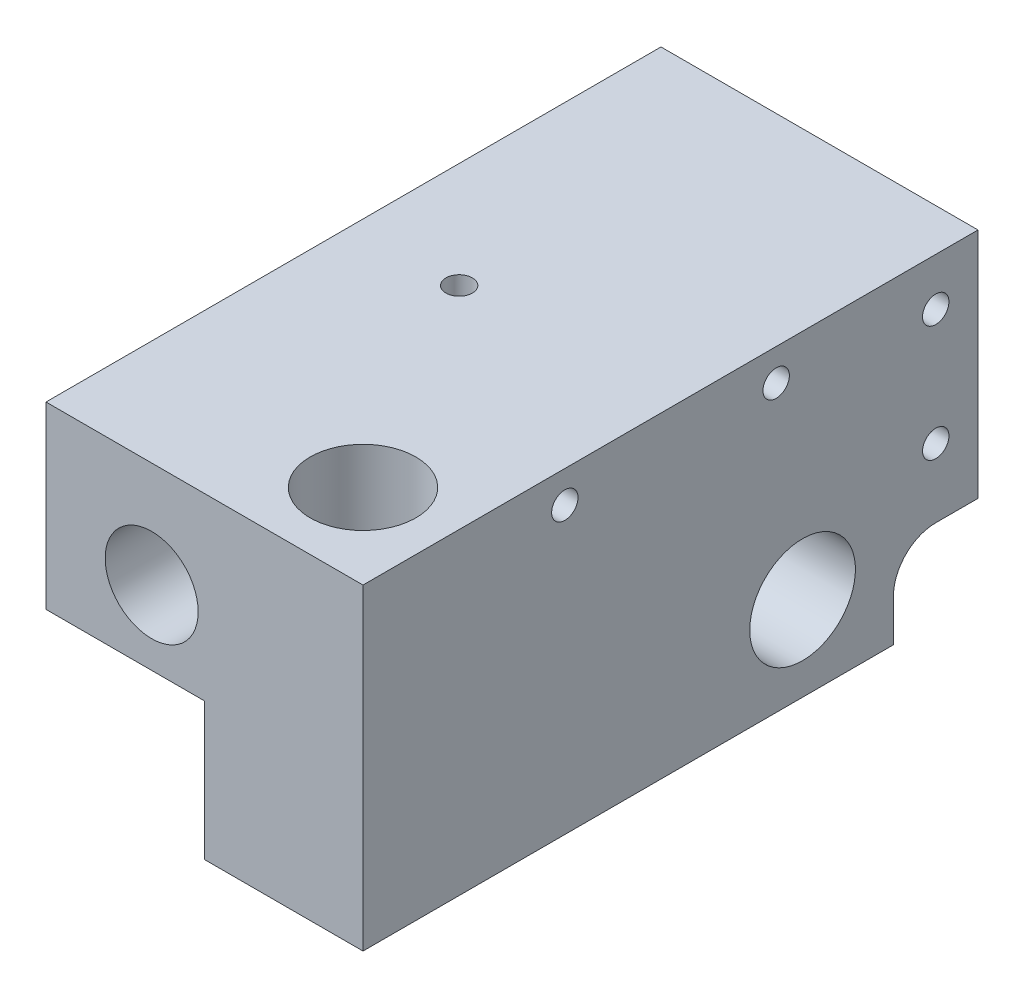
SolidWorks part; units mm, degrees
material "6061-T4 (SS)"
ref_plane "Piano frontale" through (0, 0, 0) normal (0, 0, 1) x (1, 0, 0)
ref_plane "Piano superiore" through (0, 0, 0) normal (0, 1, 0) x (1, 0, 0)
ref_plane "Piano destro" through (0, 0, 0) normal (1, 0, 0) x (0, 0, -1)
sketch "Schizzo1" plane through (0, 0, 0) normal (0, 0, 1) x (1, 0, 0)
  line L1 (0, 0) -> (30, 0)
  line L2 (0, 0) -> (0, 30)
  line L3 (0, 30) -> (30, 30)
  line L4 (30, 0) -> (30, 30)
  dimension "D1" = 30
extrude "Estrusione-Estrusione1" add sketch "Schizzo1" along normal blind 58.2
sketch "Schizzo2" plane through (0, 0, 0) normal (0, -1, 0) x (1, 0, 0)
  line L1 (0, 58.2) -> (30, 58.2) construction
  line L3 (30, 58.2) -> (30, 0) construction
  circle A0 centre (22, 50.2) radius 5
  dimension "D1" = 10
  dimension "D3" = 3
  dimension "D2" = 3
extrude "Taglio-Estrusione1" cut sketch "Schizzo2" against normal up to next
ref_point "Punto1"
sketch "Schizzo3" plane through (0, 0, 0) normal (-1, 0, 0) x (0, 0, 1)
  line L0 (50.2, 0) -> (50.2, 8) construction
  line L1 (50.2, 8) -> (16.6, 8) construction
  line L2 (58.2, 30) -> (58.2, 0) construction
  line L3 (58.2, 0) -> (0, 0) construction
  circle A0 centre (16.6, 8) radius 5
  dimension "D1" = 10
  dimension "D3" = 3
  dimension "D2" = 33.6
  dimension "D4" = 41.6
extrude "Taglio-Estrusione2" cut sketch "Schizzo3" against normal up to next
sketch "Schizzo5" plane through (0, 0, 0) normal (0, 0, -1) x (-1, 0, 0)
  line L0 (0, 30) -> (-30, 0) construction
  line L3 (0, 30) -> (-30, 30) construction
  line L5 (0, 30) -> (0, 0) construction
  circle A1 centre (-10, 20) radius 3
  dimension "D1" = 10
  dimension "D2" = 10
  dimension "D4" = 6
hole_wizard "Foro filettato G1/8-1" positions "Schizzo3D1" profile "Schizzo8" tap size "G1/8" standard "BSI"
sketch3d "Schizzo3D1"
  line L1 (30, 30, 58.2) -> (0, 30, 58.2) construction
  line L2 (0, 30, 58.2) -> (0, 0, 58.2) construction
  point P0 (10, 20, 58.2)
  dimension "D1" = 10
  dimension "D2" = 10
sketch "Schizzo8" plane through (10, 20, 58.2) normal (1, 0, 0) x (0, -1, 0)
  line L0 (0, 0) -> (0, 12.6438)
  line L1 (0, 12.6438) -> (4.4, 10)
  line L2 (4.4, 10) -> (4.4, 0)
  line L5 (4.4, 0) -> (0, 0)
  line L10 (0, 12.6438) -> (-4.4, 10) construction
  line L11 (0, -6.35) -> (0, 107.95) construction
  dimension "Tap Drill Dia." = 8.8
  dimension "Tap Drill Depth" = 10
  dimension "Drill Angle" = 118
sketch "Schizzo20" plane through (0, 0, 0) normal (-1, 0, 0) x (0, 0, 1)
  line L0 (4, 8) -> (0, 8)
  line L1 (0, 0) -> (8, 0) construction
  line L2 (0, 0) -> (0, 8) construction
  line L3 (0, 8) -> (8, 8) construction
  line L4 (8, 0) -> (8, 8) construction
  line L5 (0, 8) -> (0, 0)
  line L6 (0, 0) -> (8, 0)
  line L7 (8, 0) -> (8, 4)
  arc A1 (8, 4) -> (4, 8) centre (4, 4) ccw
  dimension "D1" = 8
  dimension "D2" = 8
  dimension "D3" = 8
extrude "Taglio-Estrusione5" cut sketch "Schizzo20" against normal blind 10
sketch "Schizzo21" plane through (30, 0, 0) normal (1, 0, 0) x (0, 0, -1)
  line L0 (-8, 0) -> (-8, 4) construction
  line L2 (-4, 8) -> (0, 8) construction
  line L3 (0, 8) -> (0, 0) construction
  line L4 (-8, 0) -> (-8, 4)
  line L5 (0, 0) -> (-8, 0)
  line L6 (-4, 8) -> (0, 8)
  line L7 (0, 8) -> (0, 0)
  arc A0 (-4, 8) -> (-8, 4) centre (-4, 4) ccw construction
  arc A1 (-4, 8) -> (-8, 4) centre (-4, 4) ccw
extrude "Taglio-Estrusione6" cut sketch "Schizzo21" against normal blind 10
sketch "Schizzo23" plane through (10, 0, 0) normal (-1, 0, 0) x (0, 0, 1)
  line L0 (0, 0) -> (8, 0) construction
  line L1 (0, 8) -> (0, 0) construction
  circle A0 centre (3, 3) radius 1.5
  point P2 (4, 0)
  dimension "D3" = 3
  dimension "D1" = 3
  dimension "D2" = 3
extrude "Taglio-Estrusione7" cut sketch "Schizzo23" against normal up to surface (10 mm away) up to face at (20, 4.1657, 4.1657)
sketch "Schizzo25" plane through (30, 0, 0) normal (1, 0, 0) x (0, 0, -1)
  line L0 (-58.2, 30) -> (0, 30) construction
  line L2 (-58.2, 0) -> (-58.2, 30) construction
  point P0 (-39.1, 27)
  point P1 (-19.1, 27)
  point P8 (-58.2, 28.5095)
  dimension "D1" = 3
  dimension "D2" = 19.1
  dimension "D3" = 39.1
hole_wizard "Foro filettato M3-2" positions "Schizzo3D2" profile "Schizzo27" tap size "M3" standard "ISO"
sketch3d "Schizzo3D2"
  point P0 (30, 27, 39.1)
  point P3 (30, 27, 19.1)
sketch "Schizzo27" plane through (30, 27, 39.1) normal (0, 1, 0) x (0, 0, -1)
  line L0 (0, 0) -> (0, 12.2511)
  line L1 (0, 12.2511) -> (1.25, 11.5)
  line L2 (1.25, 11.5) -> (1.25, 0)
  line L5 (1.25, 0) -> (0, 0)
  line L10 (0, 12.2511) -> (-1.25, 11.5) construction
  line L11 (0, -6.35) -> (0, 107.95) construction
  dimension "Tap Drill Dia." = 2.5
  dimension "Tap Drill Depth" = 11.5
  dimension "Drill Angle" = 118
cosmetic thread "Filettatura del foro2" parameters "D1"=10, "D2"=3
cosmetic thread "Filettatura del foro3" parameters "D1"=10, "D2"=3
sketch "Schizzo29" plane through (0, 0, 0) normal (-1, 0, 0) x (0, 0, 1)
  line L0 (20.2683, 0) -> (58.2, 0)
  line L1 (58.2, 0) -> (58.2, 13)
  line L2 (58.2, 13) -> (58.2, 0)
  line L5 (58.2, 0) -> (58.2, 30) construction
  line L7 (58.2, 0) -> (8, 0) construction
  line L8 (42.2, 13) -> (58.2, 13)
  arc A1 (42.2, 13) -> (20.2683, 0) centre (42.2, -12) ccw
  line M6 (8, 0) -> (58.2, 0)
  line M7 (58.2, 0) -> (58.2, 30)
  dimension "D3" = 25
  dimension "D1" = 16
  dimension "D2" = 12
extrude "Taglio-Estrusione11" cut sketch "Schizzo29" against normal blind 15 contours L8 A1 M6 M7 region at (0, 5.9257, 41.9996)
sketch "Schizzo30" plane through (0, 30, 0) normal (0, 1, 0) x (1, 0, 0)
  line L0 (10, 0) -> (10, -58.2) construction
  line L1 (30, 0) -> (0, 0) construction
  line L2 (30, -58.2) -> (30, 0) construction
  line L3 (0, -29.1) -> (30, -29.1) construction
  line L4 (0, -58.2) -> (0, 0) construction
  line L5 (30, -58.2) -> (0, -58.2) construction
  point P4 (10, -29.1)
  dimension "D1" = 20
  dimension "D2" = 29.1
hole_wizard "Foro filettato M3-3" positions "Schizzo3D4" profile "Schizzo31" tap size "M3" standard "DIN"
sketch3d "Schizzo3D4"
  point P0 (10, 30, 29.1)
  point P2 (10, 30, 29.1)
  point P4 (10, 30, 29.1)
  point P7 (10, 30, 29.1)
  point P9 (10, 30, 29.1)
sketch "Schizzo31" plane through (10, 30, 29.1) normal (1, 0, 0) x (0, 0, 1)
  line L0 (0, 0) -> (0, 5.7511)
  line L1 (0, 5.7511) -> (1.25, 5)
  line L2 (1.25, 5) -> (1.25, 0)
  line L5 (1.25, 0) -> (0, 0)
  line L10 (0, 5.7511) -> (-1.25, 5) construction
  line L11 (0, -6.35) -> (0, 107.95) construction
  dimension "Tap Drill Dia." = 2.5
  dimension "Tap Drill Depth" = 5
  dimension "Drill Angle" = 118
hole_wizard "Foro Ø16.0 (16)-1" positions "Schizzo3D5" profile "Schizzo32" hole size "Ø16.0" standard "ISO"
sketch3d "Schizzo3D5"
  point P0 (10, 20, 0)
sketch "Schizzo32" plane through (10, 20, 0) normal (1, 0, 0) x (0, 1, 0)
  line L0 (0, 0) -> (0, 15.8069)
  line L1 (0, 15.8069) -> (8, 11)
  line L2 (8, 11) -> (8, 0)
  line L5 (8, 0) -> (0, 0)
  line L10 (0, 15.8069) -> (-8, 11) construction
  line L11 (0, -6.35) -> (0, 107.95) construction
  dimension "Hole Dia." = 16
  dimension "Hole Depth" = 11
  dimension "Drill Angle" = 118
extrude "Taglio-Estrusione13" cut sketch "Schizzo5" against normal through all
sketch "Schizzo33" plane through (0, 0, 0) normal (-1, 0, 0) x (0, 0, 1)
  line L0 (11, 20) -> (0, 20) construction
  line L1 (11, 28) -> (11, 12) construction
  line L2 (0, 30) -> (0, 8) construction
  line L3 (58.2, 30) -> (0, 30) construction
  point P6 (4, 25.5)
  point P7 (4, 14.5)
  dimension "D1" = 5.5
  dimension "D2" = 7
  dimension "D3" = 4.5
  dimension "D4" = 15.5
  dimension "D5" = 4
hole_wizard "Foro filettato M3-4" positions "Schizzo3D6" profile "Schizzo34" tap size "M3" standard "ISO" end condition through all
sketch3d "Schizzo3D6"
  point P0 (0, 25.5, 4)
  point P3 (0, 14.5, 4)
sketch "Schizzo34" plane through (0, 25.5, 4) normal (0, 1, 0) x (0, 0, 1)
  line L0 (0, 0) -> (0, 30)
  line L1 (0, 30) -> (1.25, 30)
  line L2 (1.25, 30) -> (1.25, 0)
  line L5 (1.25, 0) -> (0, 0)
  line L11 (0, -6.35) -> (0, 107.95) construction
  dimension "Thread Major Dia." = 2.5
  dimension "Thru Tap Drill Depth" = 30
